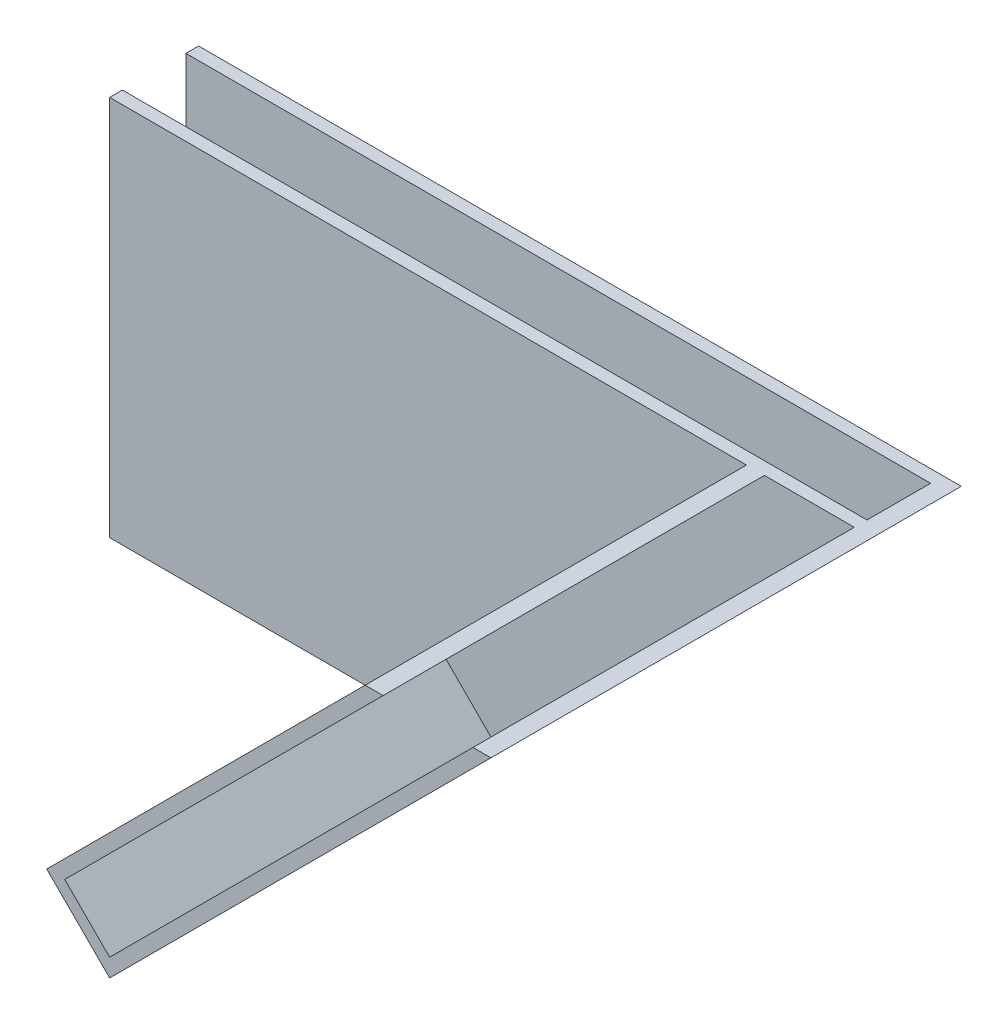
SolidWorks part; units mm, degrees
ref_plane "Front Plane" through (0, 0, 0) normal (0, 0, 1) x (1, 0, 0)
ref_plane "Top Plane" through (0, 0, 0) normal (0, 1, 0) x (1, 0, 0)
ref_plane "Right Plane" through (0, 0, 0) normal (1, 0, 0) x (0, 0, -1)
sketch "Sketch1" plane through (0, 0, 0) normal (0, 0, 1) x (1, 0, 0)
  line L1 (0, 0) -> (-30, 0)
  line L2 (0, 0) -> (0, 30)
  line L3 (0, 30) -> (-30, 30)
  line L4 (-30, 0) -> (-30, 30)
  dimension "D1" = 30
  dimension "D2" = 30
extrude "Boss-Extrude1" add sketch "Sketch1" along normal blind 7
sketch "Sketch2" plane through (0, 0, 0) normal (1, 0, 0) x (0, 0, -1)
  line L4 (0, 0) -> (0, 30)
  line L5 (0, 30) -> (-7, 30)
  line L6 (-7, 30) -> (-7, 0)
  line L7 (-7, 0) -> (0, 0)
  line L8 (0, 0) -> (0, 30)
  line L9 (0, 30) -> (-7, 30)
  line L10 (-7, 30) -> (-7, 0)
  line L11 (-7, 0) -> (0, 0)
  dimension "D1" = 0
extrude "Boss-Extrude2" add sketch "Sketch2" along normal blind 30
sketch "Sketch3" plane through (0, 0, 7) normal (0, 0, 1) x (1, 0, 0)
  line L0 (0, 0) -> (30, 30)
  line L1 (30, 30) -> (30, 0)
  line L2 (30, 0) -> (0, 0)
extrude "Cut-Extrude1" cut sketch "Sketch3" against normal blind 30
shell "Shell1" thickness 1 removed face at (-30, 15, 3.5) removed face at (0, 30, 3.5)
sketch "Sketch4" plane through (0, 0, 7) normal (0, 0, 1) x (1, 0, 0)
  line L0 (0, 0) -> (-4.9497, 4.9497)
  line L1 (-4.9497, 4.9497) -> (20.1005, 30)
  line L2 (30, 30) -> (-30, 30) construction
  line L3 (20.1005, 30) -> (30, 30)
  line L4 (30, 30) -> (0, 0)
  dimension "D1" = 7
extrude "Boss-Extrude3" add sketch "Sketch4" along normal blind 30
sketch "Sketch5" plane through (0, 0, 0) normal (0, 0, -1) x (-1, 0, 0)
  line L4 (30, 30) -> (-30, 30)
  line L5 (-30, 30) -> (0, 0)
  line L6 (0, 0) -> (30, 0)
  line L7 (30, 0) -> (30, 30)
  line L8 (30, 30) -> (-30, 30)
  line L9 (-30, 30) -> (0, 0)
  line L10 (0, 0) -> (30, 0)
  line L11 (30, 0) -> (30, 30)
  dimension "D1" = 0
shell "Shell2" thickness 1 removed face at (11.2877, 16.2374, 37) removed face at (3.7373, 30, 10.2)
